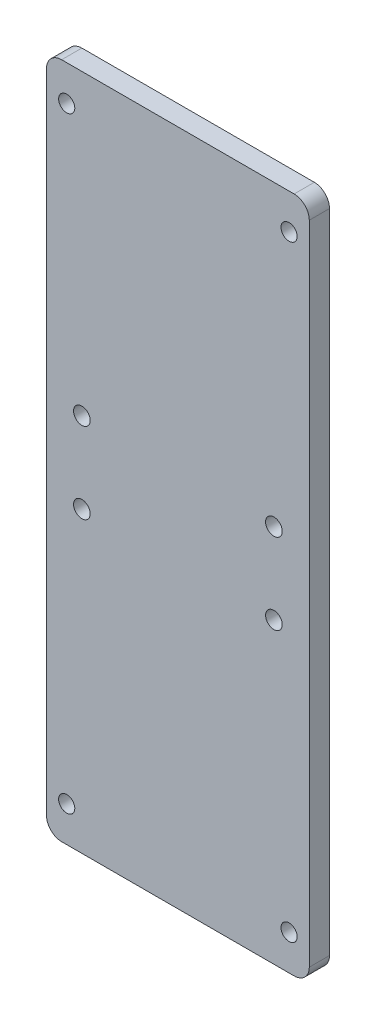
SolidWorks part; units mm, degrees
material "Acrylic (Medium-high impact)"
ref_plane "Front Plane" through (0, 0, 0) normal (0, 0, 1) x (1, 0, 0)
ref_plane "Top Plane" through (0, 0, 0) normal (0, 1, 0) x (1, 0, 0)
ref_plane "Right Plane" through (0, 0, 0) normal (1, 0, 0) x (0, 0, -1)
sketch "Sketch1" plane through (0, 0, 0) normal (0, 0, 1) x (1, 0, 0)
  line L0 (1.25, 62.9364) -> (93.1655, 62.9364) construction
  line L1 (23.2069, 126.9364) -> (23.2069, -1.0636)
  line L2 (26.2069, 129.9364) -> (72.2085, 129.9364)
  line L3 (71.2085, 2.9364) -> (71.2085, -10.0636) construction
  line L4 (26.2069, -4.0636) -> (72.2085, -4.0636)
  line L8 (49.2077, -12.0636) -> (49.2077, 137.9364) construction
  line L20 (75.2085, 126.9364) -> (75.2085, -1.0636)
  circle A0 centre (30.2077, 54.9364) radius 1.65
  circle A1 centre (27.2069, 2.9364) radius 1.6
  arc A2 (26.2069, -4.0636) -> (23.2069, -1.0636) centre (26.2069, -1.0636) cw
  circle A3 centre (68.2077, 70.9364) radius 1.65
  arc A4 (72.2085, -4.0636) -> (75.2085, -1.0636) centre (72.2085, -1.0636) ccw
  circle A5 centre (71.2085, 122.9364) radius 1.6
  arc A6 (72.2085, 129.9364) -> (75.2085, 126.9364) centre (72.2085, 126.9364) cw
  circle A7 centre (71.2085, 2.9364) radius 1.6
  arc A8 (26.2069, 129.9364) -> (23.2069, 126.9364) centre (26.2069, 126.9364) ccw
  circle A9 centre (68.2077, 54.9364) radius 1.65
  circle A10 centre (27.2069, 122.9364) radius 1.6
  circle A11 centre (30.2077, 70.9364) radius 1.65
  point P10 (23.2069, 62.9364)
  point P13 (49.2077, 129.9364)
  point P14 (49.2077, -4.0636)
  point P30 (75.2085, 62.9364)
  dimension "D5" = 22.0008
  dimension "D17" = 3
  dimension "D6" = 3.2
  dimension "D7" = 16
  dimension "D8" = 19
  dimension "D2" = 26.0008
  dimension "D3" = 67
  dimension "D4" = 60
extrude "Boss-Extrude1" add sketch "Sketch1" along normal blind 4
